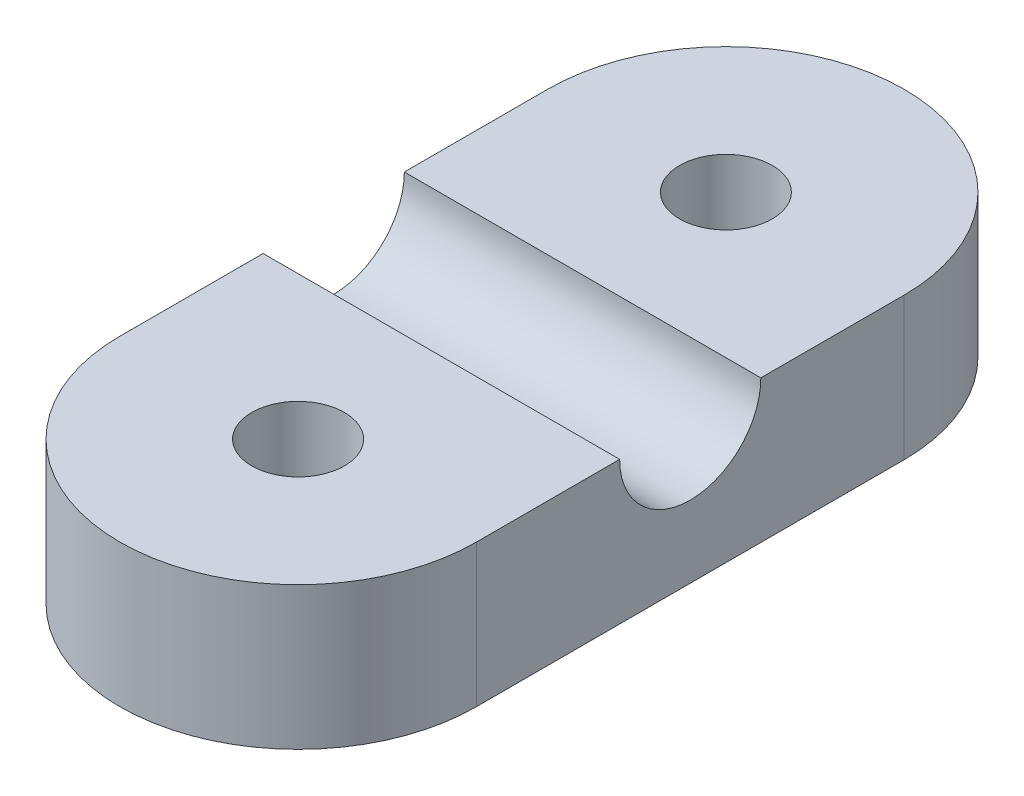
SolidWorks part; units mm, degrees
ref_plane "Front Plane" through (0, 0, 0) normal (0, 0, 1) x (1, 0, 0)
ref_plane "Top Plane" through (0, 0, 0) normal (0, 1, 0) x (1, 0, 0)
ref_plane "Right Plane" through (0, 0, 0) normal (1, 0, 0) x (0, 0, -1)
sketch "Sketch1" plane through (0, 0, 0) normal (0, 1, 0) x (1, 0, 0)
  line L0 (0, 27.5) -> (0, -27.5) construction
  line L1 (-12.5, 27.5) -> (12.5, 27.5)
  line L2 (-12.5, 27.5) -> (-12.5, -27.5)
  line L3 (-12.5, -27.5) -> (12.5, -27.5)
  line L4 (12.5, 27.5) -> (12.5, -27.5)
  line L5 (-12.5, 27.5) -> (12.5, -27.5) construction
  line L6 (-12.5, -27.5) -> (12.5, 27.5) construction
  line L7 (-12.5, 0) -> (12.5, 0) construction
  circle A0 centre (0, 15) radius 3.25
  circle A1 centre (0, -15) radius 3.25
  circle A2 centre (0, 15) radius 12.5
  circle A3 centre (0, -15) radius 12.5
  point P0 (0, 0)
  dimension "D3" = 6.5
  dimension "D1" = 25
  dimension "D4" = 30
extrude "Boss-Extrude1" add sketch "Sketch1" along normal blind 10 contours L2 A3 L4 A2 | A2 A0 | A3 A1 region at (8.5888, 0, -23.5888) region at (0, 0, 0) region at (0, 0, 2.8536)
sketch "Sketch2" plane through (12.5, 0, 0) normal (1, 0, 0) x (0, 0, -1)
  line L1 (15, 10) -> (-15, 10) construction
  circle A0 centre (0, 10) radius 4.95
  point P2 (0, 10)
  dimension "D1" = 9.9
extrude "Cut-Extrude1" cut sketch "Sketch2" against normal up to next
